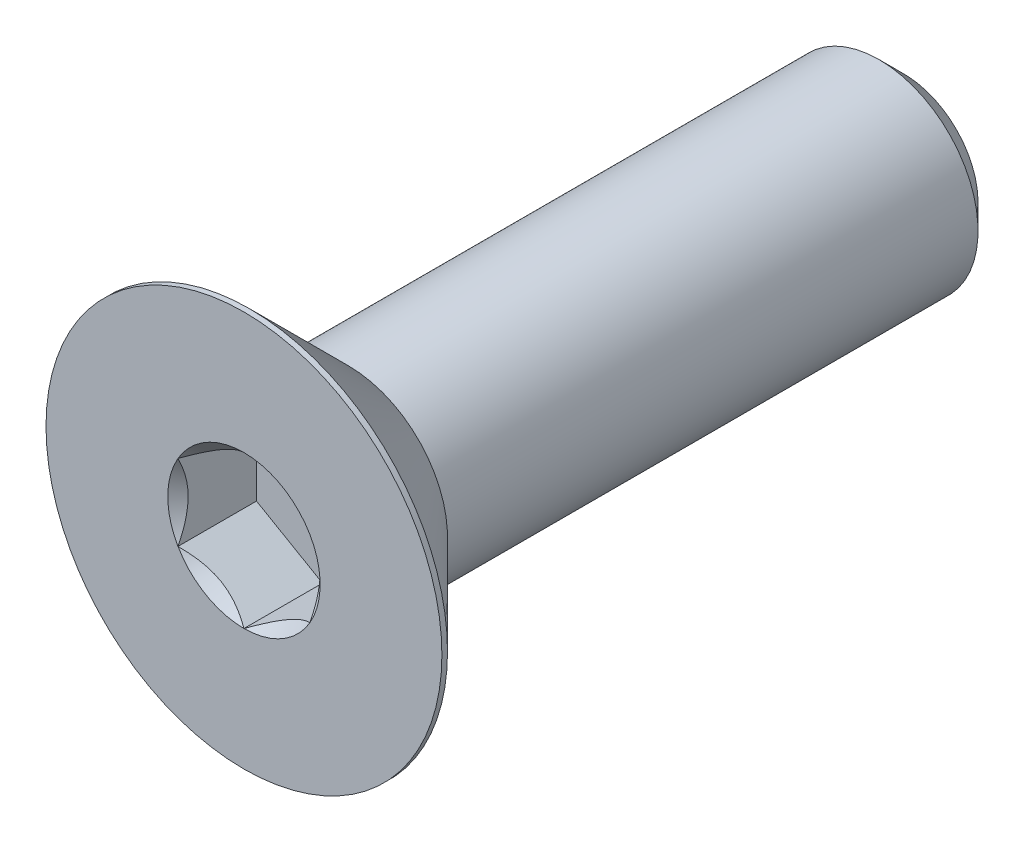
SolidWorks part; units mm, degrees
ref_plane "Front" through (0, 0, 0) normal (0, 0, 1) x (1, 0, 0)
ref_plane "Top" through (0, 0, 0) normal (0, 1, 0) x (1, 0, 0)
ref_plane "Right" through (0, 0, 0) normal (1, 0, 0) x (0, 0, -1)
sketch "Sketch11" plane through (0, 0, 0) normal (1, 0, 0) x (0, 0, -1)
  line L0 (-5, 3) -> (5, 3) construction
  line L5 (-5, 3) -> (-5, -3) construction
  line L6 (5, 1.5) -> (5, -1.5) construction
  line L7 (-4.99, 1) -> (-4.99, -1) construction
  line L8 (4.9688, 1.5541) -> (5.4688, 1.5541) construction
  line L9 (5.4688, 1.5541) -> (5.2188, 1.1211) construction
  line L10 (5.2188, 1.1211) -> (4.9688, 1.5541) construction
  line L11 (5.1875, 1.1752) -> (5.25, 1.1752) construction
  line L12 (5.2188, 1.1752) -> (5.2188, 1.1211) construction
  line L13 (4.9844, 1.5271) -> (5.4531, 1.5271) construction
  line L14 (5.2188, 1.5541) -> (5.2188, 1.5) construction
  line L15 (5, 1.5) -> (5.4375, 1.5) construction
  line L17 (-4.915, 3) -> (-1.915, 0) construction
  line L18 (-1.915, 0) -> (-4.915, -3) construction
  point P3 (-3.3, 3)
  point P8 (0, 3)
  point P21 (5.2188, 1.5271)
  point P26 (-5, 0)
  point P28 (-4.99, 0)
  point P29 (5, 0)
  dimension "Length" = 10
  dimension "Head Diameter" = 6
  dimension "Thread Major Diameter" = 3
  dimension "Head Height" = 1.7
  dimension "Drive Size" = 2
  dimension "Thread Pitch" = 0.5
  dimension "D1" = 0.0625
  dimension "D2" = 0.01
  dimension "D3" = 0.085
  dimension "Countersink Angle" = 90
sketch "Sketch1" plane through (0, 0, 0) normal (1, 0, 0) x (0, 0, -1)
  line L2 (-3.3, 1.5) -> (5, 1.5)
  line L3 (5, 1.5) -> (5, 0)
  line L4 (-3.81, 1.5) -> (-3.81, 0)
  line L5 (-3.3, 1.5) -> (-3.81, 1.5)
  line L6 (-5, 3) -> (-5, -3) construction
  line L7 (5, 1.5) -> (5, -1.5) construction
  line L8 (-3.81, 0) -> (5, 0)
  dimension "D1" = 1.19
revolve "Revolve1" add sketch "Sketch1" angle 360 mid plane about L8
chamfer "Chamfer1" distance 0.375 angle 45 1 edges at (0, -1.5, -5)
sketch "Sketch7" plane through (0, 0, 0) normal (1, 0, 0) x (0, 0, -1)
  line L2 (-5, 3) -> (-4.915, 3)
  line L5 (-3.3, 1.385) -> (-3.3, 0)
  line L6 (-5, 3) -> (-5, 0)
  line L8 (-5, 3) -> (-5, -3) construction
  line L9 (-5, 0) -> (-3.3, 0)
  line L12 (-4.915, 3) -> (-3.3, 1.385)
  line L13 (-4.915, 3) -> (-1.915, 0) construction
revolve "Revolve2" add sketch "Sketch7" angle 360 mid plane about L9 region at (0, 1.1696, 4.2571)
ref_plane "Plane1" through (0, 0, 3.3) normal (0, 0, 1) x (1, 0, 0)
sketch "Sketch5" plane through (0, 0, 5) normal (0, 0, 1) x (1, 0, 0)
  line L1 (1, -0.5774) -> (1, 0.5774)
  line L2 (1, 0.5774) -> (0, 1.1547)
  line L3 (0, 1.1547) -> (-1, 0.5774)
  line L4 (-1, 0.5774) -> (-1, -0.5774)
  line L5 (-1, -0.5774) -> (0, -1.1547)
  line L6 (0, -1.1547) -> (1, -0.5774)
  circle A0 centre (0, 0) radius 1 construction
extrude "Cut-Extrude2" cut sketch "Sketch5" against normal blind 1.19
sketch "Sketch6" plane through (0, 0, 5) normal (0, 0, -1) x (-1, 0, 0)
  circle A0 centre (0, 0) radius 1.1547
extrude "Cut-Extrude3" cut sketch "Sketch6" along normal blind 1.19 draft 45
sketch "Sketch12" plane through (0, 0, -5) normal (0, 0, -1) x (-1, 0, 0)
  circle A0 centre (0, 0) radius 1.5 construction
  circle A1 centre (0, 0) radius 1.5
curve "Helix/Spiral1" pitch 0.5 height 10 turns 20
sketch "Sketch13" plane through (0, 0, 0) normal (1, 0, 0) x (0, 0, -1)
  line L0 (4.9844, 1.5271) -> (5.4531, 1.5271)
  line L1 (5.4531, 1.5271) -> (5.25, 1.1752)
  line L2 (5.25, 1.1752) -> (5.1875, 1.1752)
  line L3 (5.1875, 1.1752) -> (4.9844, 1.5271)
sweep "Cut-Sweep1" [suppressed] cut profiles "Sketch13" path "Helix/Spiral1"
combine bodies "Combine1" operation type add bodies to combine 113 108
equation "\"D1@Chamfer1\"=\"Thread Pitch@Sketch11\" * .75"
equation "\"D1@Cut-Extrude2\"= \"Head Height@Sketch11\" * .7"
equation "\"D1@Cut-Extrude3\" = \"D1@Cut-Extrude2\""
equation "\"D1@Sketch11\"=\"Thread Pitch@Sketch11\"/8"
equation "\"D3@Sketch11\"=\"Head Height@Sketch11\"*.05"
equation "\"D4@Helix/Spiral1\"=\"Thread Pitch@Sketch11\""
equation "\"D1@Sketch1\"=\"Head Height@Sketch11\"*.7"
equation "\"D3@Helix/Spiral1\"=\"Length@Sketch11\""
